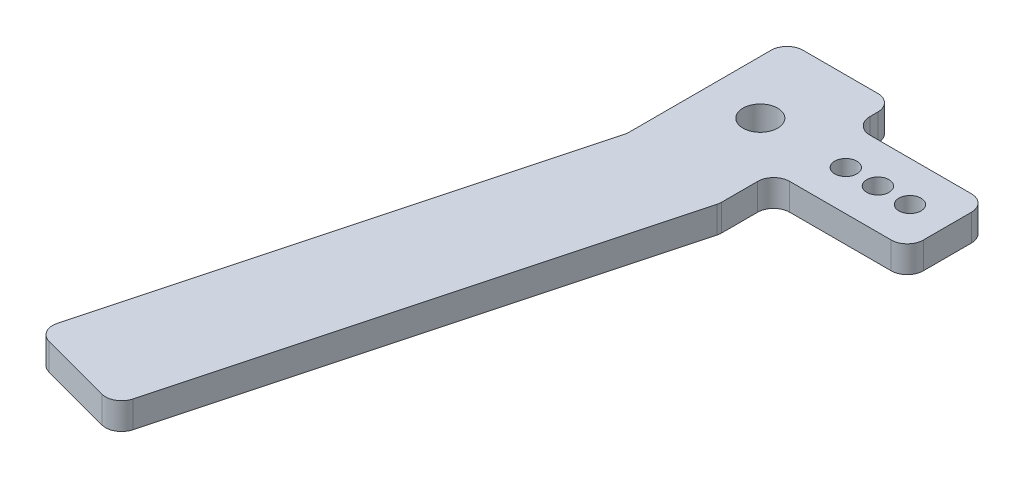
SolidWorks part; units mm, degrees
ref_plane "Front Plane" through (0, 0, 0) normal (0, 0, 1) x (1, 0, 0)
ref_plane "Top Plane" through (0, 0, 0) normal (0, 1, 0) x (1, 0, 0)
ref_plane "Right Plane" through (0, 0, 0) normal (1, 0, 0) x (0, 0, -1)
sketch "Sketch1" plane through (0, 0, 0) normal (0, 1, 0) x (1, 0, 0)
  line L0 (-30, 0) -> (-49.15, 0) construction
  line L1 (-30, -15) -> (30, -15) construction
  line L2 (-30, -15) -> (-30, 15) construction
  line L3 (-30, 15) -> (30, 15) construction
  line L4 (30, -15) -> (30, 15) construction
  line L5 (0, 15) -> (0, -15) construction
  line L6 (-30, 0) -> (30, 0) construction
  line L7 (-59.15, -15) -> (-82.4437, -101.9333)
  line L8 (-59.15, 15) -> (-39.15, 15)
  line L9 (-59.15, 15) -> (-59.15, -15)
  line L10 (-59.15, -15) -> (-39.15, -15) construction
  line L11 (-39.15, 15) -> (-39.15, -15)
  line L12 (-49.15, -15) -> (-49.15, 15) construction
  line L13 (-59.15, 0) -> (-39.15, 0) construction
  line L14 (-59.15, -15) -> (-39.8315, -20.1764) construction
  line L15 (-82.4437, -101.9333) -> (-63.1252, -107.1097)
  line L16 (-39.8315, -20.1764) -> (-63.1252, -107.1097)
  line L17 (-39.8315, -20.1764) -> (-39.15, -17.633)
  line L18 (-39.15, -15) -> (-39.15, -17.633)
  circle A0 centre (-49.15, 0) radius 3.25
  point P0 (0, 0)
  point P14 (-25, 15)
  dimension "D3" = 6.5
  dimension "D1" = 60
  dimension "D2" = 30
  dimension "D4" = 19.15
  dimension "D5" = 20
  dimension "D6" = 30
  dimension "D7" = 20
  dimension "D8" = 90
  dimension "D9" = 165
  dimension "D10" = 5
extrude "Boss-Extrude1" add sketch "Sketch1" along normal blind 5
sketch "Sketch2" plane through (0, 0, 0) normal (0, -1, 0) x (1, 0, 0)
  line L0 (-49.15, 0) -> (-26.65, 0) construction
  line L1 (-39.15, 17.633) -> (-39.15, -15) construction
  line L2 (-14.15, 7.5) -> (-39.15, 7.5)
  line L3 (-14.15, 7.5) -> (-14.15, -7.5)
  line L4 (-14.15, -7.5) -> (-39.15, -7.5)
  line L5 (-39.15, 7.5) -> (-39.15, -7.5)
  line L6 (-26.65, -7.5) -> (-26.65, 7.5) construction
  line L7 (-14.15, 0) -> (-39.15, 0) construction
  line L8 (-8.15, 7.5) -> (-33.15, 7.5)
  line L9 (-2.15, 7.5) -> (-27.15, 7.5)
  circle A0 centre (-33.15, 0) radius 2.075
  circle A1 centre (-49.15, 0) radius 3.25 construction
  circle A2 centre (-27.15, 0) radius 2.075
  circle A3 centre (-21.15, 0) radius 2.075
  line M7 (-39.15, -15) -> (-39.15, 17.633)
  dimension "D2" = 4.15
  dimension "D3" = 16
  dimension "D1" = 35
  dimension "D4" = 15
  dimension "D5" = 3
extrude "Boss-Extrude2" add sketch "Sketch2" against normal up to surface (5 mm away) contours L4 L3 L2 L8 A3 A2 A0 M7 region at (-14.4415, 0, 0) up to face at (-57.0282, 5, 35.2793)
fillet "Fillet1" radius 3 10 edges at (-59.15, 2.5, 15) (-59.15, 2.5, -15) (-39.15, 2.5, -15) (-39.15, 2.5, 17.633) (-82.4437, 2.5, 101.9333) (-63.1252, 2.5, 107.1097) (-14.15, 2.5, 7.5) (-14.15, 2.5, -7.5) (-39.15, 2.5, -7.5) (-39.15, 2.5, 7.5)
